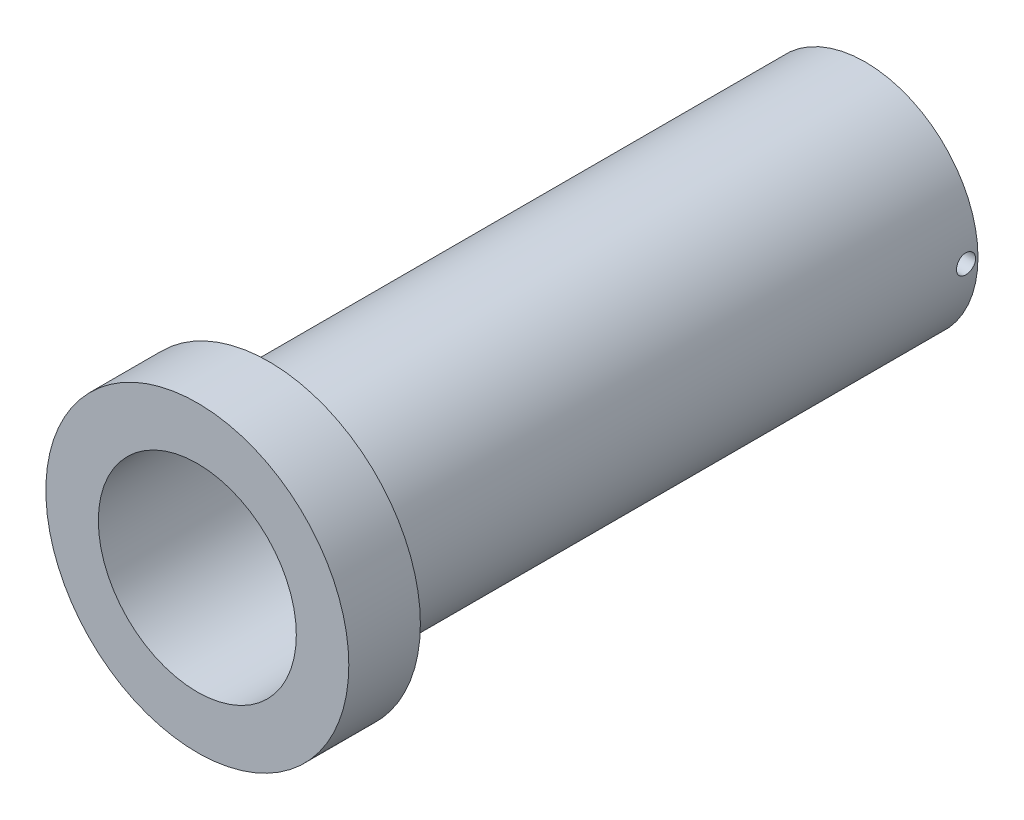
SolidWorks part; units mm, degrees
material "1060 Alloy"
ref_plane "Front Plane" through (0, 0, 0) normal (0, 0, 1) x (1, 0, 0)
ref_plane "Top Plane" through (0, 0, 0) normal (0, 1, 0) x (1, 0, 0)
ref_plane "Right Plane" through (0, 0, 0) normal (1, 0, 0) x (0, 0, -1)
sketch "Sketch1" plane through (0, 0, 0) normal (0, 0, 1) x (1, 0, 0)
  circle A0 centre (12.7336, -2.8837) radius 8.3
  circle A1 centre (12.7336, -2.8837) radius 8.25 construction
  circle A2 centre (12.7336, -2.8837) radius 9.45
  arc A3 (5.0484, 3.1163) -> (5.0484, -8.8837) centre (12.7336, -2.8837) ccw construction
  dimension "D1" = 0.05
  dimension "D2" = 0.3
extrude "Boss-Extrude1" add sketch "Sketch1" along normal blind 50
sketch "Sketch2" plane through (0, 0, 50) normal (0, 0, 1) x (1, 0, 0)
  circle A0 centre (12.7336, -2.8837) radius 8.3
  circle A1 centre (12.7336, -2.8837) radius 8.3 construction
  circle A2 centre (12.7336, -2.8837) radius 12.7
  dimension "D1" = 25.4
extrude "Boss-Extrude2" add sketch "Sketch2" along normal blind 6
sketch3d "3DSketch1" plane through (0, 0, 0) normal (0, 0, 1) x (1, 0, 0)
sketch "Sketch5" plane through (22.1836, 0, 0) normal (1, 0, 0) x (0, 0, -1)
  line L0 (-15.5677, -2.8837) -> (63.1439, -2.8837) construction
  line L1 (0, -12.3337) -> (0, 6.5663) construction
  point P0 (-1, -2.8837)
  dimension "D1" = 1
hole_wizard "M2x0.4 Tapped Hole1" positions "3DSketch4" profile "Sketch7" tap size "M2x0.4" standard "Ansi Metric" end condition through all
sketch3d "3DSketch4"
  point P0 (22.1836, -2.8837, 1)
sketch "Sketch7" plane through (22.1836, -2.8837, 1) normal (0, 1, 0) x (0, 0, -1)
  line L0 (0, 0) -> (0, 22.15)
  line L1 (0, 22.15) -> (0.8, 22.15)
  line L2 (0.8, 22.15) -> (0.8, 0)
  line L5 (0.8, 0) -> (0, 0)
  line L11 (0, -6.35) -> (0, 107.95) construction
  dimension "Thru Tap Drill Dia." = 1.6
  dimension "Thru Tap Drill Depth" = 22.15
cosmetic thread "Hole Thread1" parameters "D2"=2
